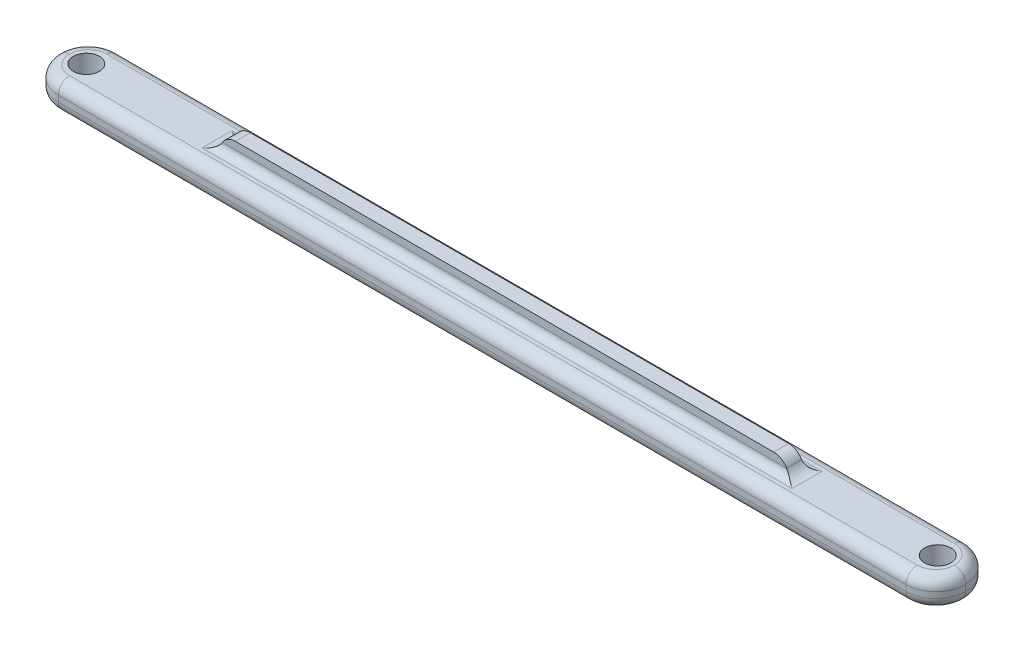
SolidWorks part; units mm, degrees
material "ABS"
ref_plane "Front Plane" through (0, 0, 0) normal (0, 0, 1) x (1, 0, 0)
ref_plane "Top Plane" through (0, 0, 0) normal (0, 1, 0) x (1, 0, 0)
ref_plane "Right Plane" through (0, 0, 0) normal (1, 0, 0) x (0, 0, -1)
sketch "Sketch1" plane through (0, 0, 0) normal (0, 1, 0) x (1, 0, 0)
  line L1 (-60.75, 4) -> (60.75, 4)
  line L2 (-60.75, 4) -> (-60.75, -4)
  line L3 (-60.75, -4) -> (60.75, -4)
  line L4 (60.75, 4) -> (60.75, -4)
  line L5 (-60.75, 4) -> (60.75, -4) construction
  line L6 (-60.75, -4) -> (60.75, 4) construction
  point P0 (0, 0)
  dimension "D1" = 8
  dimension "D2" = 121.5
extrude "Boss-Extrude1" add sketch "Sketch1" along normal blind 3.8
sketch "Sketch2" plane through (0, 3.8, 0) normal (0, 1, 0) x (1, 0, 0)
  line L0 (0, 0) -> (-57, 0) construction
  line L1 (0, 0) -> (57, 0) construction
  circle A0 centre (-57, 0) radius 1.75
  circle A1 centre (57, 0) radius 1.75
  dimension "D3" = 3.5
  dimension "D4" = 3.5
  dimension "D1" = 57
  dimension "D2" = 57
extrude "Cut-Extrude4" cut sketch "Sketch2" against normal through all
fillet "Fillet1" radius 4 4 edges at (60.75, 1.9, -4) (60.75, 1.9, 4) (-60.75, 1.9, 4) (-60.75, 1.9, -4)
fillet "Fillet2" radius 1.5 12 edges at (59.5784, 0, -2.8284) (59.5784, 0, 2.8284) (0, 0, 4) (-59.5784, 0, 2.8284) (-59.5784, 0, -2.8284) (59.5784, 3.8, -2.8284) (59.5784, 3.8, 2.8284) (0, 3.8, 4) (-59.5784, 3.8, 2.8284) (-59.5784, 3.8, -2.8284) (0, 0, -4) (0, 3.8, -4)
sketch "Sketch3" plane through (0, 3.8, 0) normal (0, 1, 0) x (1, 0, 0)
  line L1 (-37.5, 1) -> (37.5, 1)
  line L2 (-37.5, 1) -> (-37.5, -1)
  line L3 (-37.5, -1) -> (37.5, -1)
  line L4 (37.5, 1) -> (37.5, -1)
  line L5 (-37.5, 1) -> (37.5, -1) construction
  line L6 (-37.5, -1) -> (37.5, 1) construction
  point P0 (0, 0)
  dimension "D1" = 75
  dimension "D2" = 2
extrude "Boss-Extrude2" add sketch "Sketch3" along normal blind 2 and the other way blind 5.8
fillet "Fillet3" radius 2 4 edges at (-37.5, 0, 0) (37.5, 0, 0) (-37.5, 3.8, 0) (37.5, 3.8, 0)
fillet "Fillet4" radius 2 4 edges at (-37.5, 5.8, 0) (-37.5, -2, 0) (37.5, -2, 0) (37.5, 5.8, 0)
fillet "Fillet5" radius 1 4 edges at (0, 3.8, -1) (0, 3.8, 1) (0, 0, 1) (0, 0, -1)
